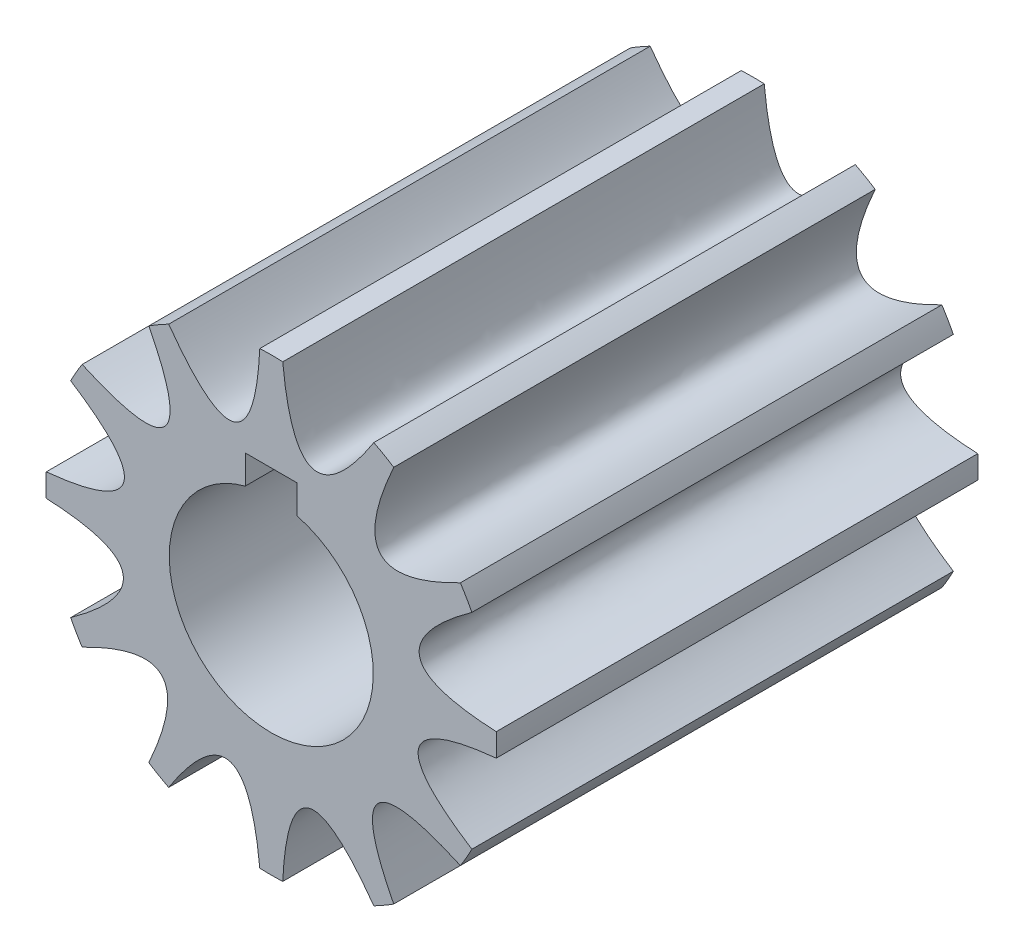
SolidWorks part; units mm, degrees
material "Vex Aluminum Spur Gear"
ref_plane "Front Plane" through (0, 0, 0) normal (0, 0, 1) x (1, 0, 0)
ref_plane "Top Plane" through (0, 0, 0) normal (0, 1, 0) x (1, 0, 0)
ref_plane "Right Plane" through (0, 0, 0) normal (1, 0, 0) x (0, 0, -1)
ref_plane "Plane1" through (0, 0, -9.4996) normal (0, 0, -1) x (-1, 0, 0)
sketch "Sketch1" plane through (0, 0, -9.4996) normal (0, 0, -1) x (-1, 0, 0)
  line L0 (-1.0254, 3.8926) -> (-1.0254, 5.0254)
  line L1 (-1.0254, 5.0254) -> (1.0254, 5.0254)
  line L2 (1.0254, 5.0254) -> (1.0254, 3.8926)
  arc A0 (-4.0467, 7.9156) -> (-4.8317, 7.4624) centre (0, 0) ccw
  arc A1 (-7.4624, 4.8317) -> (-7.9156, 4.0467) centre (0, 0) ccw
  arc A2 (-8.8784, 0.4532) -> (-8.8784, -0.4532) centre (0, 0) ccw
  arc A3 (-7.9156, -4.0467) -> (-7.4624, -4.8317) centre (0, 0) ccw
  arc A4 (-4.8317, -7.4624) -> (-4.0467, -7.9156) centre (0, 0) ccw
  arc A5 (-0.4532, -8.8784) -> (0.4532, -8.8784) centre (0, 0) ccw
  arc A6 (4.0467, -7.9156) -> (4.8317, -7.4624) centre (0, 0) ccw
  arc A7 (7.4624, -4.8317) -> (7.9156, -4.0467) centre (0, 0) ccw
  arc A8 (8.8784, -0.4532) -> (8.8784, 0.4532) centre (0, 0) ccw
  arc A9 (7.9156, 4.0467) -> (7.4624, 4.8317) centre (0, 0) ccw
  arc A10 (4.8317, 7.4624) -> (4.0467, 7.9156) centre (0, 0) ccw
  arc A11 (0.4532, 8.8784) -> (-0.4532, 8.8784) centre (0, 0) ccw
  arc A12 (1.0254, 3.8926) -> (-1.0254, 3.8926) centre (0, 0) cw
  ellipse E0 centre (-48.4605, 203.4487) end of major axis (-1.6577, 5.8135) minor radius 11.5476 (-4.0467, 7.9156) -> (-0.4532, 8.8784) ccw
  ellipse E1 centre (-143.8952, 152.1722) end of major axis (-283.4482, 300.1385) minor radius 11.5559 (-7.4624, 4.8317) -> (-4.8317, 7.4624) ccw
  ellipse E2 centre (-200.4222, 59.7564) end of major axis (-394.9809, 118.0417) minor radius 11.5476 (-8.8784, 0.4532) -> (-7.9156, 4.0467) ccw
  ellipse E3 centre (-203.449, -48.4605) end of major axis (-401.0844, -95.2634) minor radius 11.5476 (-7.9156, -4.0467) -> (-8.8784, -0.4532) ccw
  ellipse E4 centre (-151.9617, -143.6925) end of major axis (-4.2058, -4.3424) minor radius 11.5476 (-4.8317, -7.4624) -> (-7.4624, -4.8317) ccw
  ellipse E5 centre (-59.7564, -200.4222) end of major axis (-118.0417, -394.9809) minor radius 11.5476 (-0.4532, -8.8784) -> (-4.0467, -7.9156) ccw
  ellipse E6 centre (48.4605, -203.449) end of major axis (95.2634, -401.0844) minor radius 11.5476 (4.0467, -7.9156) -> (0.4532, -8.8784) ccw
  ellipse E7 centre (143.6925, -151.9617) end of major axis (283.0426, -299.7176) minor radius 11.5476 (7.4624, -4.8317) -> (4.8317, -7.4624) ccw
  ellipse E8 centre (200.4222, -59.7564) end of major axis (5.8635, -1.4712) minor radius 11.5476 (8.8784, -0.4532) -> (7.9156, -4.0467) ccw
  ellipse E9 centre (203.449, 48.4605) end of major axis (401.0844, 95.2634) minor radius 11.5476 (7.9156, 4.0467) -> (8.8784, 0.4532) ccw
  ellipse E10 centre (151.9617, 143.6925) end of major axis (299.7175, 283.0426) minor radius 11.5476 (4.8317, 7.4624) -> (7.4624, 4.8317) ccw
  ellipse E11 centre (59.7565, 200.4223) end of major axis (1.4712, 5.8635) minor radius 11.5476 (0.4532, 8.8784) -> (4.0467, 7.9156) ccw
  point P0 (-48.4605, 203.4487)
  point P1 (-59.6973, 200.7877)
  point P2 (-1.6577, 5.8135)
  point P3 (-4.0467, 7.9156)
  point P4 (-0.4532, 8.8784)
  point P5 (-1.434, 5.8712)
  point P6 (-95.4869, 401.0263)
  point P16 (-143.8952, 152.1722)
  point P17 (-152.302, 144.2434)
  point P18 (-4.3423, 4.2059)
  point P19 (-7.4624, 4.8317)
  point P20 (-4.8317, 7.4624)
  point P21 (-4.1775, 4.3675)
  point P22 (-283.6129, 299.9769)
  point P30 (-200.4222, 59.7564)
  point P31 (-394.9809, 118.0417)
  point P32 (-203.7361, 48.6945)
  point P33 (-8.8784, 0.4532)
  point P34 (-7.9156, 4.0467)
  point P35 (-5.8016, 1.6937)
  point P36 (-395.0429, 117.8192)
  point P44 (-203.449, -48.4605)
  point P45 (-401.0844, -95.2634)
  point P46 (-200.7879, -59.6974)
  point P47 (-7.9156, -4.0467)
  point P48 (-8.8784, -0.4532)
  point P49 (-5.8712, -1.434)
  point P50 (-401.0268, -95.487)
  point P58 (-151.9617, -143.6925)
  point P59 (-299.7176, -283.0427)
  point P60 (-144.0388, -152.0934)
  point P61 (-4.8317, -7.4624)
  point P62 (-7.4624, -4.8317)
  point P63 (-4.3676, -4.1775)
  point P64 (-299.5559, -283.2076)
  point P72 (-59.7564, -200.4222)
  point P73 (-70.8184, -197.1083)
  point P74 (-118.0417, -394.9809)
  point P75 (-0.4532, -8.8784)
  point P76 (-4.0467, -7.9156)
  point P77 (-1.6937, -5.8016)
  point P78 (-117.8192, -395.0428)
  point P86 (48.4605, -203.449)
  point P87 (37.2237, -206.11)
  point P88 (95.2634, -401.0844)
  point P89 (4.0467, -7.9156)
  point P90 (0.4532, -8.8784)
  point P91 (1.434, -5.8712)
  point P92 (95.487, -401.0268)
  point P100 (143.6925, -151.9617)
  point P101 (135.2916, -159.8847)
  point P102 (283.0426, -299.7176)
  point P103 (7.4624, -4.8317)
  point P104 (4.8317, -7.4624)
  point P105 (4.1775, -4.3676)
  point P106 (283.2075, -299.5558)
  point P114 (200.4222, -59.7564)
  point P115 (5.8635, -1.4712)
  point P116 (197.1083, -70.8184)
  point P117 (8.8784, -0.4532)
  point P118 (7.9156, -4.0467)
  point P119 (5.8016, -1.6937)
  point P120 (395.0428, -117.8192)
  point P128 (203.449, 48.4605)
  point P129 (5.8135, 1.6577)
  point P130 (206.11, 37.2237)
  point P131 (7.9156, 4.0467)
  point P132 (8.8784, 0.4532)
  point P133 (5.8712, 1.434)
  point P134 (401.0268, 95.487)
  point P142 (151.9617, 143.6925)
  point P143 (4.2058, 4.3424)
  point P144 (159.8846, 135.2916)
  point P145 (4.8317, 7.4624)
  point P146 (7.4624, 4.8317)
  point P147 (4.3676, 4.1775)
  point P148 (299.5558, 283.2075)
  point P156 (59.7565, 200.4223)
  point P157 (48.6945, 203.7361)
  point P158 (1.4712, 5.8635)
  point P159 (0.4532, 8.8784)
  point P160 (4.0467, 7.9156)
  point P161 (1.6937, 5.8016)
  point P162 (117.8192, 395.0429)
extrude "Boss-Extrude1" add sketch "Sketch1" against normal blind 18.9992
ref_axis "Pinion" through (0, 0, 9.4996) along (0, 0, -1)
